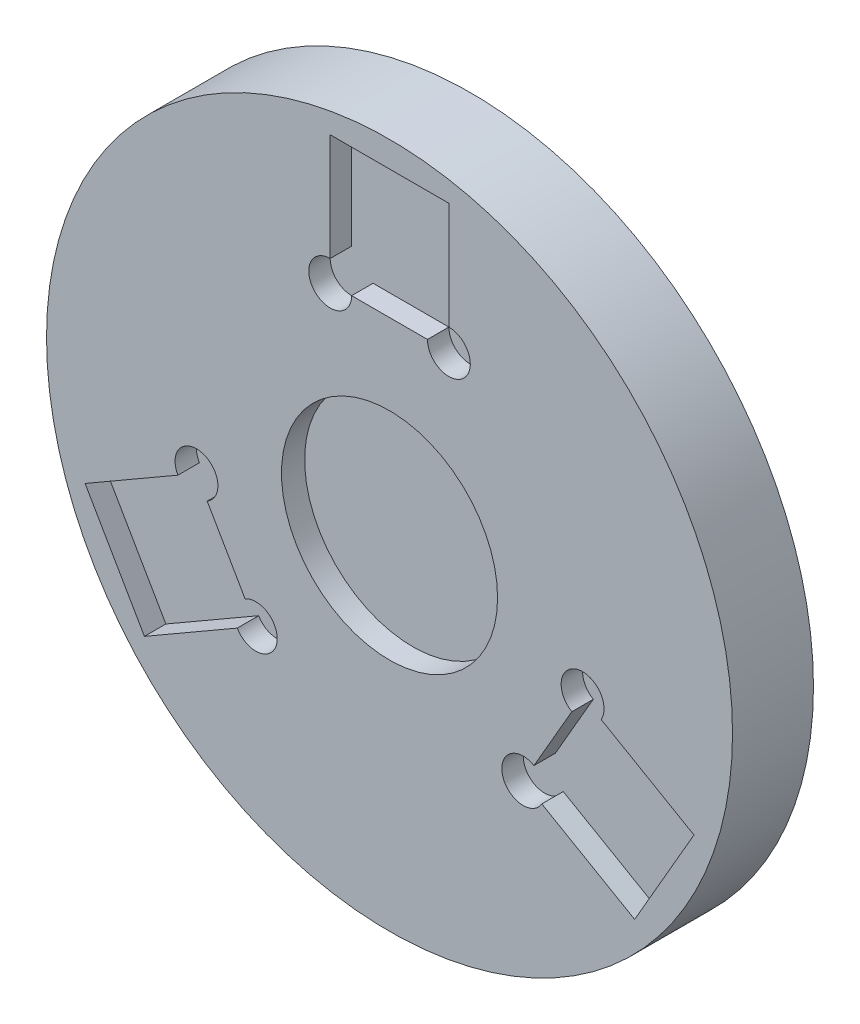
SolidWorks part; units mm, degrees
material "Beech"
ref_plane "Front Plane" through (0, 0, 0) normal (0, 0, 1) x (1, 0, 0)
ref_plane "Top Plane" through (0, 0, 0) normal (0, 1, 0) x (1, 0, 0)
ref_plane "Right Plane" through (0, 0, 0) normal (1, 0, 0) x (0, 0, -1)
sketch "Sketch1" plane through (0, 0, 0) normal (0, 0, 1) x (1, 0, 0)
  line L1 (-50.8, 50.8) -> (50.8, 50.8) construction
  line L2 (-50.8, 50.8) -> (-50.8, -50.8) construction
  line L3 (-50.8, -50.8) -> (50.8, -50.8) construction
  line L4 (50.8, 50.8) -> (50.8, -50.8) construction
  line L5 (-50.8, 50.8) -> (50.8, -50.8) construction
  line L6 (-50.8, -50.8) -> (50.8, 50.8) construction
  circle A0 centre (0, 0) radius 50.8
  point P0 (0, 0)
  dimension "D1" = 101.6
extrude "Boss-Extrude1" add sketch "Sketch1" along normal blind 11.9888
sketch "coupling circle" plane through (0, 0, 11.9888) normal (0, 0, 1) x (1, 0, 0)
  circle A0 centre (0, 0) radius 38.1
  dimension "D1" = 76.2
sketch "Sketch3" plane through (0, 0, 11.9888) normal (0, 0, 1) x (1, 0, 0)
  line L1 (-8.7871, 46.99) -> (8.7871, 46.99)
  line L2 (-8.7871, 46.99) -> (-8.7871, 27.94)
  line L3 (-8.7871, 27.94) -> (8.7871, 27.94)
  line L4 (8.7871, 46.99) -> (8.7871, 27.94)
  line L5 (-8.7871, 46.99) -> (8.7871, 27.94) construction
  line L6 (-8.7871, 27.94) -> (8.7871, 46.99) construction
  circle A1 centre (0, 0) radius 38.1 construction
  point P0 (0, 37.465)
  dimension "D1" = 17.5743
  dimension "D2" = 10.16
  dimension "D3" = 19.05
extrude "pocket" cut sketch "Sketch3" against normal blind 3.175
ref_axis "Axis1" through (0, 0, 11.9888) along (0, 0, 1)
sketch "Sketch7" plane through (0, 0, 11.9888) normal (0, 0, 1) x (1, 0, 0)
  circle A0 centre (-8.7871, 27.94) radius 3.175
  circle A1 centre (8.7871, 27.94) radius 3.175
  dimension "D1" = 6.35
extrude "corner relief" cut sketch "Sketch7" against normal up to surface (3.175 mm away) up to face at (0, 37.465, 8.8138)
pattern_circular "CirPattern1" count 3 over 360 about axis through (0, 0, 11.9888) along (0, 0, 1) of "pocket", "corner relief"
sketch "Sketch5" plane through (0, 0, 11.9888) normal (0, 0, 1) x (1, 0, 0)
  circle A0 centre (0, 0) radius 16.002
  dimension "D1" = 32.004
extrude "magnet inset" cut sketch "Sketch5" against normal blind 3.429
sketch "Sketch6" [suppressed] plane through (0, 0, 8.8138) normal (0, 0, 1) x (1, 0, 0)
  circle A0 centre (0, 0) radius 3.175
  dimension "D1" = 6.35
extrude "Cut-Extrude4" [suppressed] cut sketch "Sketch6" against normal through all
